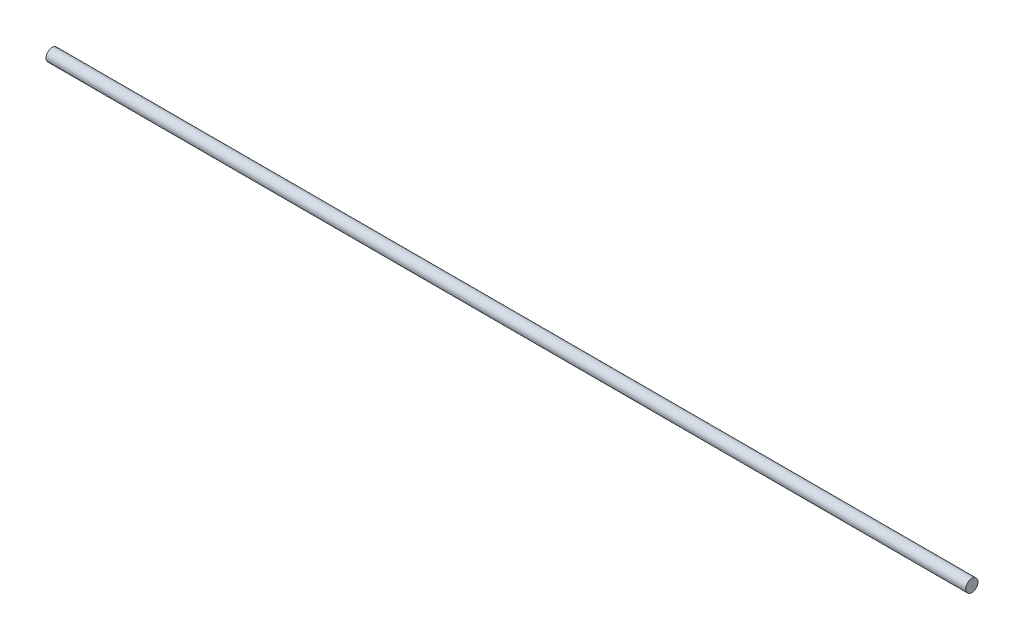
SolidWorks part; units mm, degrees
ref_plane "Front Plane" through (0, 0, 0) normal (0, 0, 1) x (1, 0, 0)
ref_plane "Top Plane" through (0, 0, 0) normal (0, 1, 0) x (1, 0, 0)
ref_plane "Right Plane" through (0, 0, 0) normal (1, 0, 0) x (0, 0, -1)
sketch "Sketch1" plane through (0, 0, 0) normal (1, 0, 0) x (0, 0, -1)
  circle A0 centre (0, 0) radius 4
  dimension "D1" = 8
extrude "Boss-Extrude1" add sketch "Sketch1" along normal blind 600
